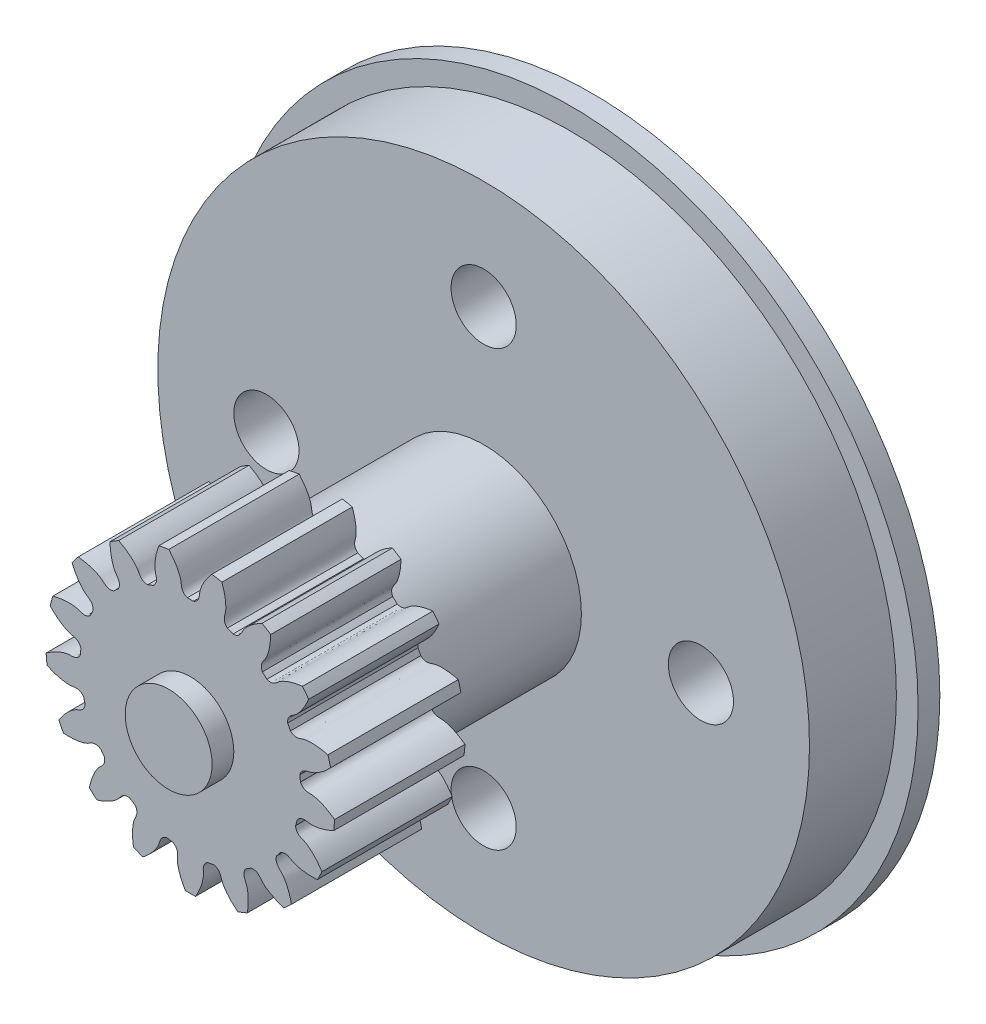
SolidWorks part; units mm, degrees
material "40Cr"
ref_plane "前视基准面" through (0, 0, 0) normal (0, 0, 1) x (1, 0, 0)
ref_plane "上视基准面" through (0, 0, 0) normal (0, 1, 0) x (1, 0, 0)
ref_plane "右视基准面" through (0, 0, 0) normal (1, 0, 0) x (0, 0, -1)
sketch "草图1" plane through (0, 0, 0) normal (0, 0, 1) x (1, 0, 0)
  circle A0 centre (0, 0) radius 6.65
ref_axis "基准轴1" through (0, 0, -7.315) along (0, 0, 1)
sketch "草图2" plane through (0, 0, 0) normal (0, 0, 1) x (1, 0, 0)
  line L0 (0, 0) -> (0, 6.65) construction
  circle A0 centre (0, 0) radius 6.65 construction
  arc A1 (0.1412, 5.073) -> (-0.1412, 5.073) centre (0, 0) ccw
  arc A2 (2.181, 7.5185) -> (-2.181, 7.5185) centre (0, 0) ccw
  spline S0 degree 3 poles (0.1412, 5.073) (0.4395, 5.1974) (0.3963, 5.4284) (0.4468, 5.6454) (0.4515, 5.6638) (0.4571, 5.6843) (0.4638, 5.7068) (0.4716, 5.7313) (0.4806, 5.7578) (0.4909, 5.7862) (0.5026, 5.8164) (0.5157, 5.8485) (0.5303, 5.8824) (0.5466, 5.918) (0.5645, 5.9553) (0.5841, 5.9942) (0.6056, 6.0347) (0.629, 6.0767) (0.6544, 6.1202) (0.6817, 6.1651) (0.7112, 6.2113) (0.7428, 6.2587) (0.7767, 6.3074) (0.8128, 6.3572) (0.8513, 6.408) (0.8921, 6.4598) (0.9354, 6.5125) (0.9812, 6.566) (1.0296, 6.6203) (1.0805, 6.6753) (1.1341, 6.7308) (1.1904, 6.7868) (1.2494, 6.8432) (1.3112, 6.8999) (1.3757, 6.9569) (1.4431, 7.014) (1.5134, 7.0712) (1.5866, 7.1283) (1.6626, 7.1853) (1.7416, 7.2421) (1.8236, 7.2986) (1.9086, 7.3546) (2.0271, 7.4294) (2.1186, 7.4834) (2.181, 7.5185) knots 0 0 0 0 0.193883 0.199024 0.204851 0.211363 0.21856 0.226443 0.235011 0.244265 0.254205 0.264829 0.27614 0.288136 0.300817 0.314184 0.328236 0.342973 0.358397 0.374505 0.391299 0.408779 0.426944 0.445795 0.465331 0.485552 0.506459 0.528051 0.550329 0.573293 0.596941 0.621276 0.646296 0.672001 0.698392 0.725468 0.753229 0.781677 0.810809 0.840627 0.871131 0.90232 0.934195 1 1 1 1
  spline S1 degree 3 poles (-0.1412, 5.073) (-0.4395, 5.1974) (-0.3963, 5.4284) (-0.4468, 5.6454) (-0.4515, 5.6638) (-0.4571, 5.6843) (-0.4638, 5.7068) (-0.4716, 5.7313) (-0.4806, 5.7578) (-0.4909, 5.7862) (-0.5026, 5.8164) (-0.5157, 5.8485) (-0.5303, 5.8824) (-0.5466, 5.918) (-0.5645, 5.9553) (-0.5841, 5.9942) (-0.6056, 6.0347) (-0.629, 6.0767) (-0.6544, 6.1202) (-0.6817, 6.1651) (-0.7112, 6.2113) (-0.7428, 6.2587) (-0.7767, 6.3074) (-0.8128, 6.3572) (-0.8513, 6.408) (-0.8921, 6.4598) (-0.9354, 6.5125) (-0.9812, 6.566) (-1.0296, 6.6203) (-1.0805, 6.6753) (-1.1341, 6.7308) (-1.1904, 6.7868) (-1.2494, 6.8432) (-1.3112, 6.8999) (-1.3757, 6.9569) (-1.4431, 7.014) (-1.5134, 7.0712) (-1.5866, 7.1283) (-1.6626, 7.1853) (-1.7416, 7.2421) (-1.8236, 7.2986) (-1.9086, 7.3546) (-2.0271, 7.4294) (-2.1186, 7.4834) (-2.181, 7.5185) knots 0 0 0 0 0.193883 0.199024 0.204851 0.211363 0.21856 0.226443 0.235011 0.244265 0.254205 0.264829 0.27614 0.288136 0.300817 0.314184 0.328236 0.342973 0.358397 0.374505 0.391299 0.408779 0.426944 0.445795 0.465331 0.485552 0.506459 0.528051 0.550329 0.573293 0.596941 0.621276 0.646296 0.672001 0.698392 0.725468 0.753229 0.781677 0.810809 0.840627 0.871131 0.90232 0.934195 1 1 1 1
extrude "凸台-拉伸1" add sketch "草图1" along normal blind 6
extrude "切除-拉伸1" cut sketch "草图2" along normal blind 6
pattern_circular "阵列(圆周)1" count 17 every 21.176 about axis through (0, 0, -7.315) along (0, 0, 1) of "切除-拉伸1"
sketch "草图3" plane through (0, 0, 0) normal (0, 0, 1) x (1, 0, 0)
  circle A0 centre (0, 0) radius 5.95 construction
  dimension "Dn" = 11.9
sketch "草图4" plane through (0, 0, 0) normal (1, 0, 0) x (0, 0, -1)
  line L0 (0, 0) -> (27.9545, 0) construction
  line L1 (0, 0) -> (0, 4.5)
  line L2 (0, 4.5) -> (7.5, 4.5)
  line L3 (7.5, 4.5) -> (7.5, 15)
  line L4 (7.5, 15) -> (11.5, 15)
  line L5 (11.5, 15) -> (11.5, 16)
  line L6 (11.5, 16) -> (12.5, 16)
  line L7 (12.5, 16) -> (12.5, 3)
  line L8 (10, 0) -> (0, 0)
  line L9 (12.5, 3) -> (10, 3)
  line L10 (10, 3) -> (10, 0)
  dimension "D1" = 30
  dimension "D2" = 1
  dimension "D3" = 5
  dimension "D4" = 1
  dimension "D5" = 9
  dimension "D6" = 12.5
  dimension "D7" = 2.5
  dimension "D8" = 6
revolve "旋转1" add sketch "草图4" angle 360 about L0
sketch "草图5" plane through (0, 0, -7.5) normal (0, 0, 1) x (1, 0, 0)
  circle A0 centre (0, 0) radius 10 construction
  circle A1 centre (10, 0) radius 1.5
  circle A2 centre (0, -10) radius 1.5
  circle A3 centre (-10, 0) radius 1.5
  circle A4 centre (0, 10) radius 1.5
  point P14 (0, 0)
  dimension "D1" = 3
  dimension "D2" = 20
  dimension "D3" = 4
extrude "切除-拉伸2" cut sketch "草图5" against normal through all
sketch "草图6" plane through (0, 0, 6) normal (0, 0, 1) x (1, 0, 0)
  circle A0 centre (0, 0) radius 2
  dimension "D1" = 4
extrude "凸台-拉伸2" add sketch "草图6" along normal blind 1
